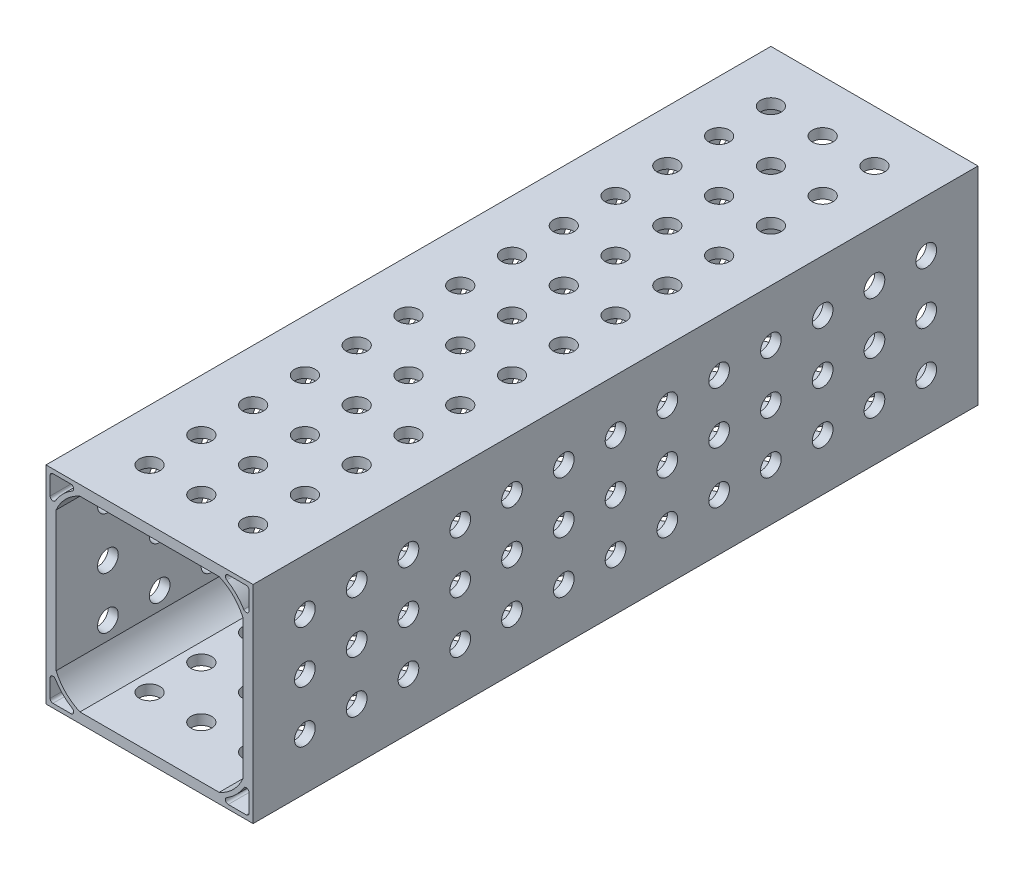
SolidWorks part; units mm, degrees
material "6061 Alloy"
ref_plane "Front Plane" through (0, 0, 0) normal (0, 0, 1) x (1, 0, 0)
ref_plane "Top Plane" through (0, 0, 0) normal (0, 1, 0) x (1, 0, 0)
ref_plane "Right Plane" through (0, 0, 0) normal (1, 0, 0) x (0, 0, -1)
other "Configuration Table"
sketch "Sketch1" plane through (0, 0, 0) normal (0, 0, 1) x (1, 0, 0)
  line L1 (-25.4, -25.4) -> (25.4, -25.4)
  line L2 (-25.4, -25.4) -> (-25.4, 25.4)
  line L3 (-25.4, 25.4) -> (25.4, 25.4)
  line L4 (25.4, -25.4) -> (25.4, 25.4)
  line L5 (-25.4, -25.4) -> (25.4, 25.4) construction
  line L6 (-25.4, 25.4) -> (25.4, -25.4) construction
  point P0 (0, 0)
  dimension "D1" = 50.8
extrude "Boss-Extrude1" add sketch "Sketch1" along normal mid plane 177.8
sketch "Sketch2" plane through (0, 0, 88.9) normal (0, 0, 1) x (1, 0, 0)
  line L10 (0, 0) -> (0, 22.9141)
  line L11 (-22.9141, 0) -> (0, 0)
  line L12 (-22.9141, 17.0772) -> (-22.9141, 0)
  line L13 (0, 22.9141) -> (-17.0772, 22.9141)
  line L14 (-24.384, 23.6924) -> (-24.384, 19.2971)
  line L15 (-19.2971, 24.384) -> (-23.6924, 24.384)
  line L16 (25.4, -25.4) -> (25.4, 25.4) construction
  arc A12 (-17.0772, 22.9141) -> (-22.9141, 17.0772) centre (-12.7, 12.7) ccw
  arc A13 (-18.9412, 23.0994) -> (-23.0994, 18.9412) centre (-12.7, 12.7) ccw
  arc A14 (-24.384, 19.2971) -> (-23.0994, 18.9412) centre (-23.6924, 19.2971) ccw
  arc A15 (-23.6924, 24.384) -> (-24.384, 23.6924) centre (-23.6924, 23.6924) ccw
  arc A16 (-18.6055, 23.6924) -> (-19.2971, 24.384) centre (-19.2971, 23.6924) ccw
  arc A17 (-18.9412, 23.0994) -> (-18.6055, 23.6924) centre (-19.2971, 23.6924) ccw
  dimension "D1" = 11.1125
  dimension "D2" = 12.1285
  dimension "D3" = 0.6916
  dimension "D4" = 12.7
  dimension "D5" = 42.4772
  dimension "D6" = 44.0055
extrude "Cut-Extrude1" cut sketch "Sketch2" against normal through all
mirror "Mirror1" about plane through (0, 0, 0) normal (1, 0, 0) of "Cut-Extrude1" second plane through (0, 0, 0) second plane normal (0, 1, 0)
sketch "Sketch4" plane through (0, 25.4, 0) normal (0, 1, 0) x (1, 0, 0)
  line L0 (25.4, -88.9) -> (-25.4, -88.9) construction
  line L1 (-25.4, -88.9) -> (-25.4, 88.9) construction
  circle A0 centre (-12.7, -76.2) radius 2.54
  dimension "D1" = 2.54
  dimension "D2" = 12.7
  dimension "D3" = 12.7
extrude "Cut-Extrude2" cut sketch "Sketch4" against normal through all
pattern_linear "LPattern1" count 13 spacing 12.7 along (0, 0, -1) count 3 spacing 12.7 along (1, 0, 0) of "Cut-Extrude2"
ref_plane "Plane1" through (0, 0, 0) normal (-0.7071, 0.7071, 0) x (0.7071, 0.7071, 0)
mirror "Mirror2" about plane through (0, 0, 0) normal (-0.7071, 0.7071, 0) of "LPattern1"
equation "\"Length\" = 7"
equation "\"D1@Boss-Extrude1\"= \"Length\""
